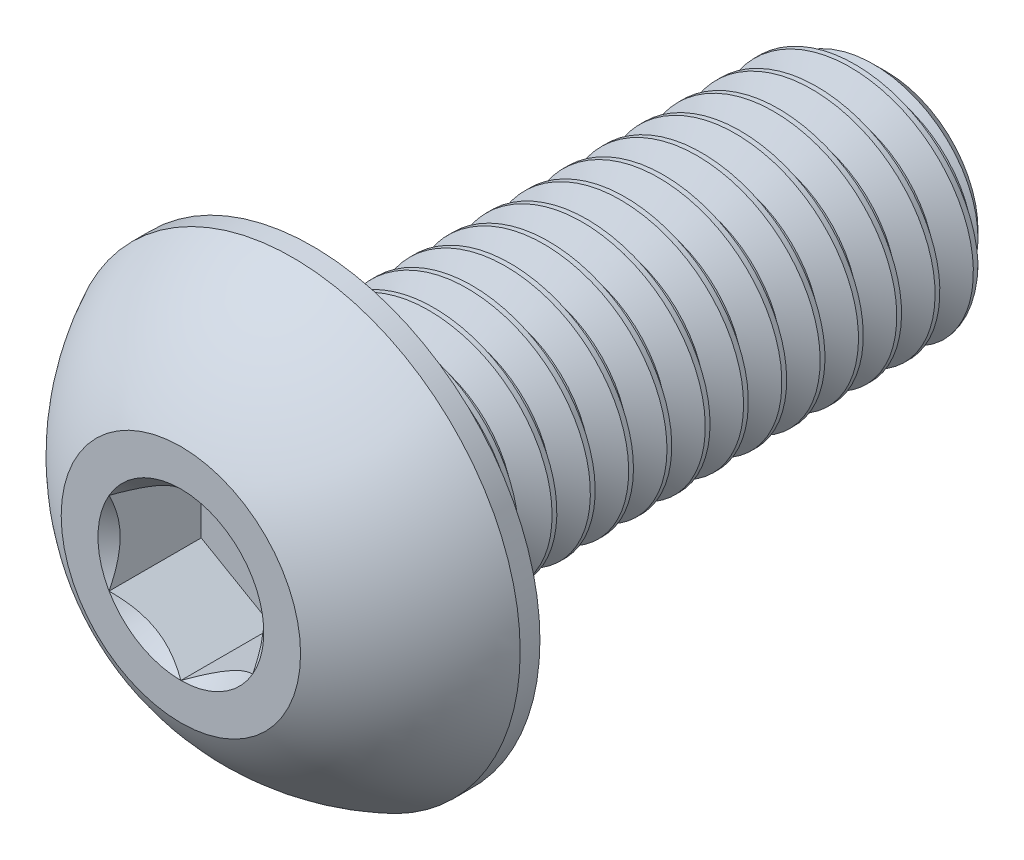
SolidWorks part; units mm, degrees
ref_plane "Front" through (0, 0, 0) normal (0, 0, 1) x (1, 0, 0)
ref_plane "Top" through (0, 0, 0) normal (0, 1, 0) x (1, 0, 0)
ref_plane "Right" through (0, 0, 0) normal (1, 0, 0) x (0, 0, -1)
sketch "Sketch1" plane through (0, 0, 0) normal (1, 0, 0) x (0, 0, -1)
  line L2 (2.75, 2.5) -> (14.75, 2.5)
  line L3 (14.75, 2.5) -> (14.75, 0)
  line L4 (14.75, 0) -> (2.75, 0)
  line L6 (2.3375, 4.75) -> (2.75, 4.75) construction
  line L7 (14.75, 2.5) -> (14.75, -2.5) construction
  line L8 (0, 0) -> (2.75, 0) construction
  line L9 (2.75, 4.75) -> (2.75, -4.75) construction
  line L11 (2.75, 2.5) -> (2.75, 0)
  line L13 (0, 1.5) -> (0, -1.5) construction
  line L14 (0, 1.5) -> (0, 2.5) construction
  arc A3 (0, 2.5) -> (2.3375, 4.75) centre (4.6581, 0) cw construction
  dimension "D1" = 0.4125
  dimension "Head Ht" = 2.75
  dimension "Head Dia" = 9.5
  dimension "Dia" = 5
  dimension "Lg" = 12
  dimension "Hex" = 3
revolve "Revolve1" add sketch "Sketch1" angle 360 about L4
sketch "Sketch3" plane through (0, 0, -14.75) normal (0, 0, -1) x (-1, 0, 0)
  circle A0 centre (0, 0) radius 2.5
curve "Helix/Spiral1" pitch 0.8 height 12.8 radius 2.5 centre (0, 0, -14.75) axis (0, 0, 1) start towards (0, 1, 0)
sketch "Sketch2" plane through (0, 0, 0) normal (1, 0, 0) x (0, 0, -1)
  line L0 (14.75, 2.5) -> (15.45, 2.5)
  line L1 (15.45, 2.5) -> (15.15, 1.9804)
  line L2 (15.15, 1.9804) -> (15.05, 1.9804)
  line L3 (15.05, 1.9804) -> (14.75, 2.5)
  line L4 (14.9, 2.2402) -> (15.3, 2.2402) construction
  dimension "D1" = 60
  dimension "D2" = 0.1
  dimension "D3" = 0.4
chamfer "Chamfer1" distance 0.6 angle 45 1 edges at (0, 2.5, -14.75)
sweep "Cut-Sweep1" cut profiles "Sketch2" path "Helix/Spiral1"
sketch "Sketch7" plane through (0, 0, 0) normal (1, 0, 0) x (0, 0, -1)
  line L6 (2.3375, 4.75) -> (2.75, 4.75) construction
  line L8 (0, 0) -> (2.75, 0) construction
  line L11 (2.75, 4.75) -> (2.75, -4.75) construction
  line L12 (2.3375, 4.75) -> (2.75, 4.75)
  line L13 (0, 0) -> (2.75, 0)
  line L14 (0, 1.5) -> (0, -1.5) construction
  line L15 (2.75, 4.75) -> (2.75, 0)
  line L16 (0, 2.5) -> (0, 0)
  arc A2 (2.3375, 4.75) -> (0, 2.5) centre (4.6581, 0) ccw construction
  arc A3 (2.3375, 4.75) -> (0, 2.5) centre (4.6581, 0) ccw
revolve "Revolve2" add sketch "Sketch7" angle 360 about L13
sketch "Sketch5" plane through (0, 0, 0) normal (0, 0, 1) x (1, 0, 0)
  line L1 (1.5, -0.866) -> (1.5, 0.866)
  line L2 (1.5, 0.866) -> (0, 1.7321)
  line L3 (0, 1.7321) -> (-1.5, 0.866)
  line L4 (-1.5, 0.866) -> (-1.5, -0.866)
  line L5 (-1.5, -0.866) -> (0, -1.7321)
  line L6 (0, -1.7321) -> (1.5, -0.866)
  circle A0 centre (0, 0) radius 1.5 construction
extrude "Cut-Extrude2" cut sketch "Sketch5" against normal blind 1.925
sketch "Sketch6" plane through (0, 0, 0) normal (0, 0, 1) x (1, 0, 0)
  circle A0 centre (0, 0) radius 1.7321
extrude "Cut-Extrude3" cut sketch "Sketch6" against normal blind 1.925 draft 45
sketch "Sketch9" [suppressed] plane through (0, 0, -6.6) normal (0, 0, 1) x (1, 0, 0)
  circle A2 centre (0, 0) radius 6
extrude "Boss-Extrude2" [suppressed] add sketch "Sketch9" against normal offset from surface (19 mm away) 32
sketch "Sketch10" plane through (0, 0, 0) normal (1, 0, 0) x (0, 0, -1)
  line L0 (14.75, 2.5) -> (14.75, -2.5) construction
  point P0 (13.55, -2.5)
  dimension "D1" = 1.2
equation "\"D3@Helix/Spiral1\" = \"Lg@Sketch1\" + \"D4@Helix/Spiral1\""
equation "\"D2@Sketch2\" = \"D4@Helix/Spiral1\" * .125"
equation "\"D3@Sketch2\" = \"D4@Helix/Spiral1\" * .5"
equation "\"D1@Chamfer1\" = \"D4@Helix/Spiral1\" * .75"
equation "\"D1@Cut-Extrude2\" = \"Head Ht@Sketch1\" * .7"
equation "\"D1@Sketch1\" = \"Head Ht@Sketch1\" * .15"
equation "\"D1@Sketch10\" = \"D4@Helix/Spiral1\" * 1.5"
equation "\"D1@Cut-Extrude3\" = \"D1@Cut-Extrude2\""
